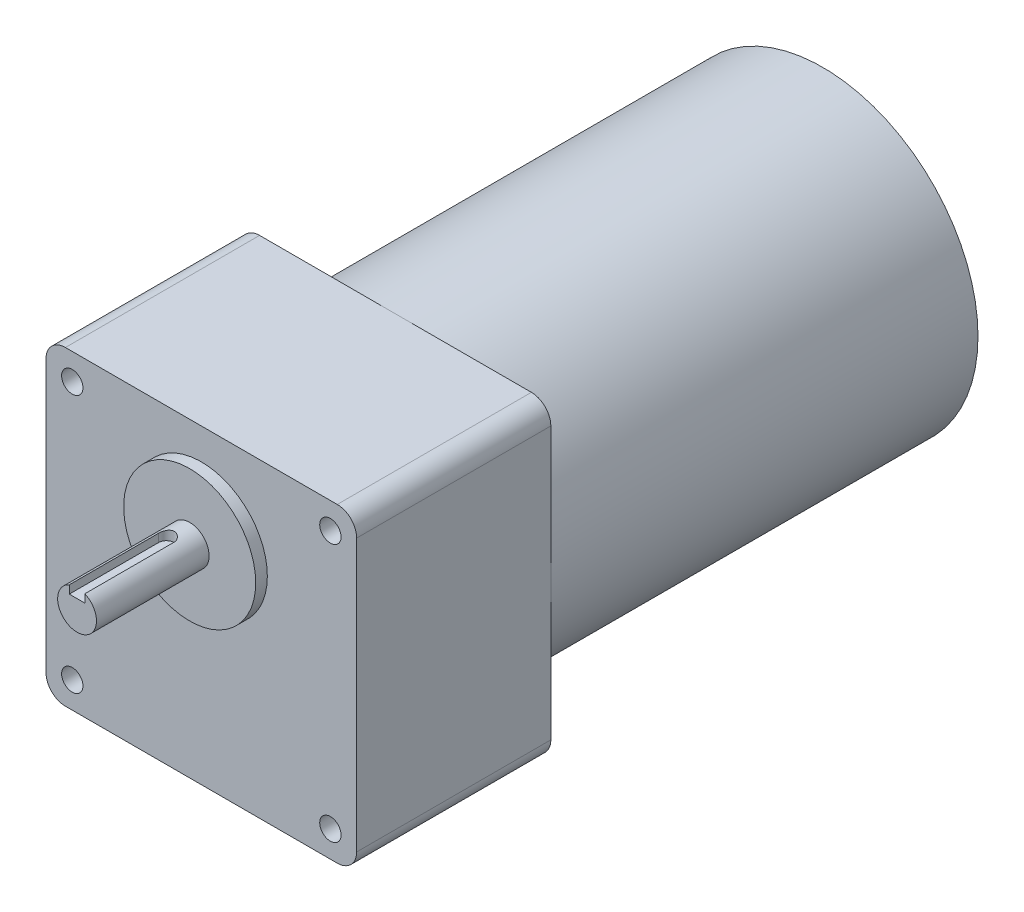
SolidWorks part; units mm, degrees
ref_plane "정면" through (0, 0, 0) normal (0, 0, 1) x (1, 0, 0)
ref_plane "윗면" through (0, 0, 0) normal (0, 1, 0) x (1, 0, 0)
ref_plane "우측면" through (0, 0, 0) normal (1, 0, 0) x (0, 0, -1)
sketch "스케치1" plane through (0, 0, 0) normal (0, 0, 1) x (1, 0, 0)
  line L1 (-40, 40) -> (40, 40)
  line L2 (-40, 40) -> (-40, -40)
  line L3 (-40, -40) -> (40, -40)
  line L4 (40, 40) -> (40, -40)
  point P0 (0, 0)
  dimension "D1" = 80
  dimension "D2" = 80
extrude "보스-돌출1" add sketch "스케치1" along normal blind 12
sketch "스케치2" plane through (0, 0, 12) normal (0, 0, 1) x (1, 0, 0)
  circle A0 centre (0, 15) radius 17
extrude "보스-돌출2" add sketch "스케치2" along normal blind 3
sketch "스케치3" plane through (0, 0, 15) normal (0, 0, 1) x (1, 0, 0)
  circle A0 centre (0, 15) radius 5
extrude "보스-돌출3" add sketch "스케치3" along normal blind 29
sketch "스케치4" plane through (0, 0, 44) normal (0, 0, 1) x (1, 0, 0)
  line L1 (0, 17.5) -> (-2, 17.5)
  line L2 (0, 17.5) -> (2, 17.5)
  line L3 (-2, 17.5) -> (-2, 20.9127)
  line L4 (-2, 20.9127) -> (2, 20.9127)
  line L5 (2, 20.9127) -> (2, 17.5)
extrude "컷-돌출1" cut sketch "스케치4" against normal blind 23
ref_plane "평면1" through (0, 20, 0) normal (0, 1, 0) x (1, 0, 0)
sketch "스케치6" plane through (0, 20, 0) normal (0, 1, 0) x (1, 0, 0)
  line L1 (-2, -21) -> (-2, -52.4077)
  line L2 (-2, -52.4077) -> (2, -52.4077)
  line L3 (2, -21) -> (2, -44) construction
  line L4 (2, -52.4077) -> (2, -21)
  arc A0 (-2, -21) -> (2, -21) centre (0, -21) cw
extrude "컷-돌출4" cut sketch "스케치6" against normal blind 2.5
sketch "스케치7" plane through (0, 0, 0) normal (0, 0, -1) x (-1, 0, 0)
  line L16 (-40, 40) -> (-40, -40)
  line L17 (-40, -40) -> (40, -40)
  line L18 (40, -40) -> (40, 40)
  line L19 (40, 40) -> (-40, 40)
  line L20 (-40, 40) -> (-40, -40)
  line L21 (-40, -40) -> (40, -40)
  line L22 (40, -40) -> (40, 40)
  line L23 (40, 40) -> (-40, 40)
  dimension "D1" = 0
extrude "보스-돌출6" add sketch "스케치7" along normal blind 38
sketch "스케치10" plane through (0, 0, -38) normal (0, 0, -1) x (-1, 0, 0)
  circle A0 centre (0, 0) radius 40
extrude "보스-돌출7" add sketch "스케치10" along normal blind 110
sketch "스케치11" plane through (0, 0, -148) normal (0, 0, -1) x (-1, 0, 0)
  circle A0 centre (0, 0) radius 14
  dimension "D1" = 28
extrude "보스-돌출8" add sketch "스케치11" along normal blind 4.5
sketch "스케치12" plane through (0, 0, 12) normal (0, 0, 1) x (1, 0, 0)
  line L0 (-33.234, 33.234) -> (0, 0) construction
  circle A0 centre (33.234, 33.234) radius 2.75
  circle A1 centre (-33.234, 33.234) radius 2.75
  circle A2 centre (-33.234, -33.234) radius 2.75
  circle A3 centre (33.234, -33.234) radius 2.75
  point P0 (0, 0)
  dimension "D3" = 5.5
  dimension "D1" = 5.5
  dimension "D2" = 5.5
  dimension "D4" = 5.5
  dimension "D5" = 47
  dimension "D6" = 47
  dimension "D7" = 47
  dimension "D8" = 47
extrude "컷-돌출5" cut sketch "스케치12" against normal through all
fillet "필렛1" radius 5 4 edges at (-40, 40, -13) (-40, -40, -13) (40, -40, -13) (40, 40, -13)
